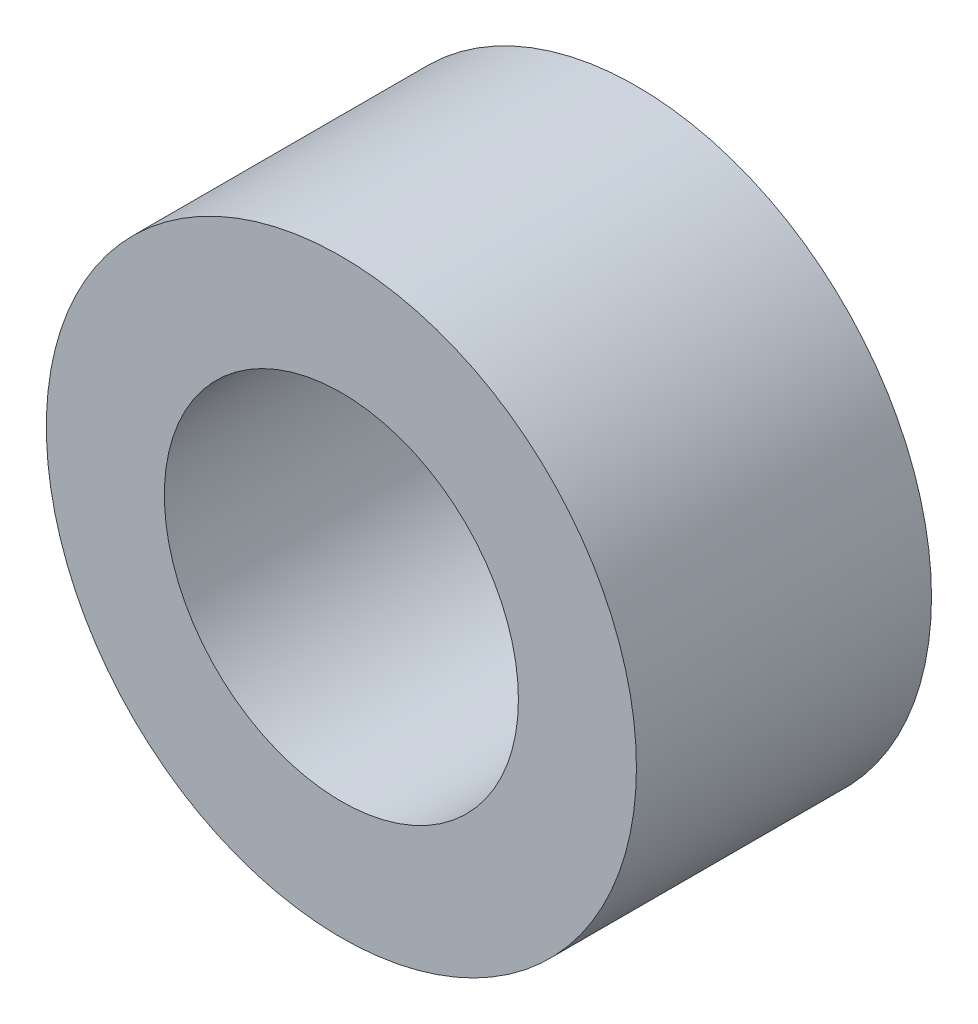
SolidWorks part; units mm, degrees
ref_plane "Piano frontale" through (0, 0, 0) normal (0, 0, 1) x (1, 0, 0)
ref_plane "Piano superiore" through (0, 0, 0) normal (0, 1, 0) x (1, 0, 0)
ref_plane "Piano destro" through (0, 0, 0) normal (1, 0, 0) x (0, 0, -1)
sketch "Schizzo1" plane through (0, 0, 0) normal (0, 0, 1) x (1, 0, 0)
  circle A0 centre (0, 0) radius 25
  circle A1 centre (0, 0) radius 15
  point P4 (0, 0)
extrude "Estrusione-Estrusione1" add sketch "Schizzo1" along normal blind 25
